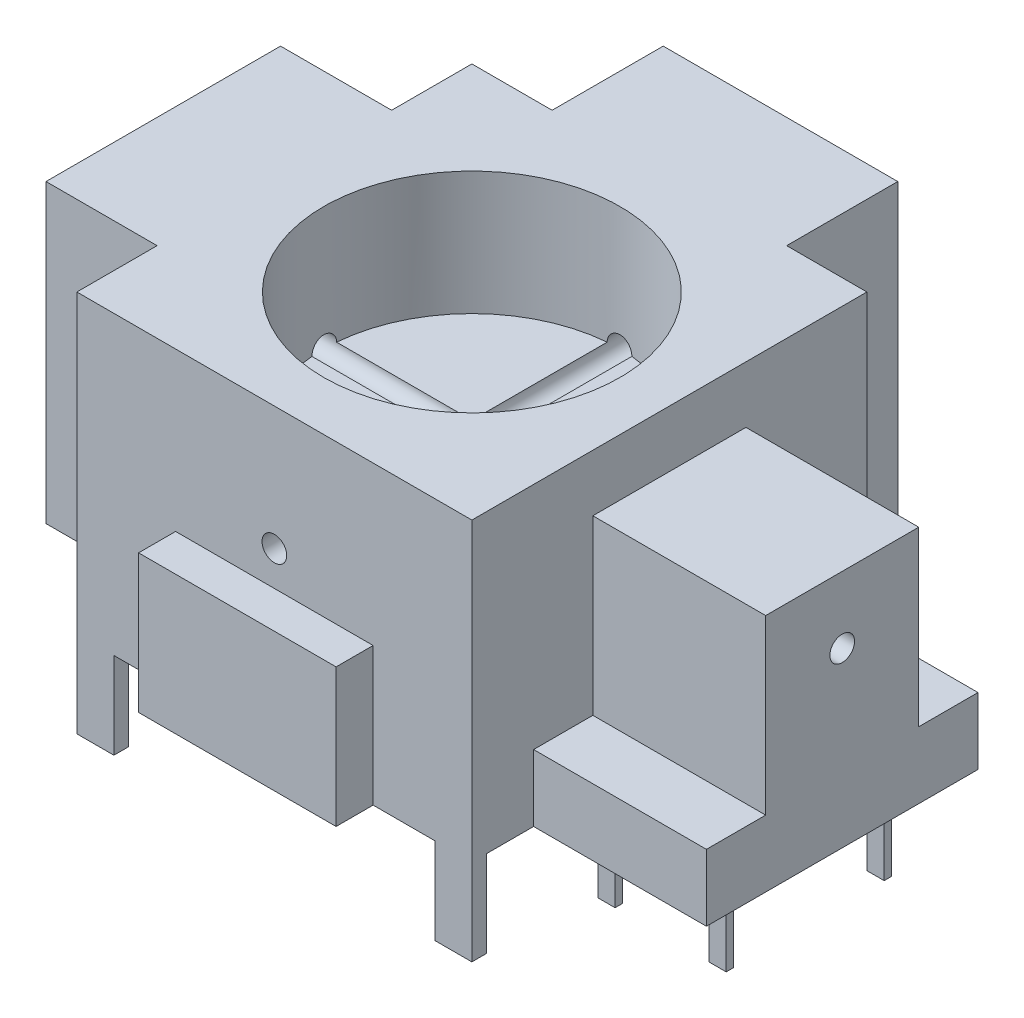
SolidWorks part; units mm, degrees
ref_plane "Front Plane" through (0, 0, 0) normal (0, 0, 1) x (1, 0, 0)
ref_plane "Top Plane" through (0, 0, 0) normal (0, 1, 0) x (1, 0, 0)
ref_plane "Right Plane" through (0, 0, 0) normal (1, 0, 0) x (0, 0, -1)
sketch "Sketch1" plane through (0, 0, 0) normal (0, 1, 0) x (1, 0, 0)
  line L1 (-8, -8) -> (8, -8)
  line L2 (-8, -8) -> (-8, 8)
  line L3 (-8, 8) -> (8, 8)
  line L4 (8, -8) -> (8, 8)
  line L5 (-8, -8) -> (8, 8) construction
  line L6 (-8, 8) -> (8, -8) construction
  point P0 (0, 0)
  dimension "D1" = 16
  dimension "D2" = 16
extrude "Boss-Extrude1" add sketch "Sketch1" along normal blind 12
sketch "Sketch2" plane through (-8, 0, 0) normal (-1, 0, 0) x (0, 0, 1)
  line L0 (-8, 0) -> (8, 0) construction
  line L1 (-4.75, 0) -> (4.75, 0)
  line L2 (-4.75, 0) -> (-4.75, 12)
  line L3 (-4.75, 12) -> (4.75, 12)
  line L4 (4.75, 0) -> (4.75, 12)
  line L5 (-8, 12) -> (8, 12) construction
  point P6 (0, 0)
  point P7 (0, 0)
  dimension "D1" = 9.5
extrude "Boss-Extrude2" add sketch "Sketch2" along normal blind 4.5
ref_axis "Axis1" through (0, 12.6, 0) along (0, -1, 0)
pattern_circular "CirPattern1" count 2 every 90 about axis through (0, 12.6, 0) along (0, -1, 0) of "Boss-Extrude2"
sketch "Sketch4" plane through (0, 0, 8) normal (0, 0, 1) x (1, 0, 0)
  line L0 (-8, 0) -> (8, 0) construction
  line L1 (-4, 0) -> (4, 0)
  line L2 (-4, 0) -> (-4, 5.6)
  line L3 (-4, 5.6) -> (4, 5.6)
  line L4 (4, 0) -> (4, 5.6)
  point P6 (0, 0)
  point P7 (0, 0)
  dimension "D1" = 5.6
  dimension "D2" = 8
extrude "Boss-Extrude3" add sketch "Sketch4" along normal blind 1.5
sketch "Sketch5" plane through (8, 0, 0) normal (1, 0, 0) x (0, 0, -1)
  line L0 (-8, 0) -> (8, 0) construction
  line L1 (-5.5, 0) -> (5.5, 0)
  line L2 (-5.5, 0) -> (-5.5, 2.7)
  line L3 (-5.5, 2.7) -> (5.5, 2.7)
  line L4 (5.5, 0) -> (5.5, 2.7)
  point P6 (0, 0)
  point P7 (0, 0)
  dimension "D1" = 11
  dimension "D2" = 2.7
extrude "Boss-Extrude4" add sketch "Sketch5" along normal blind 7
sketch "Sketch6" plane through (0, 2.7, 0) normal (0, 1, 0) x (1, 0, 0)
  line L0 (8, 5.5) -> (8, -5.5) construction
  line L1 (8, -3.1) -> (15, -3.1)
  line L2 (8, -3.1) -> (8, 3.1)
  line L3 (8, 3.1) -> (15, 3.1)
  line L4 (15, -3.1) -> (15, 3.1)
  line L5 (15, 5.5) -> (15, -5.5) construction
  point P8 (8, 0)
  point P9 (8, 0)
  dimension "D1" = 6.2
extrude "Boss-Extrude5" add sketch "Sketch6" along normal blind 7
sketch "Sketch7" plane through (0, 12, 0) normal (0, 1, 0) x (1, 0, 0)
  circle A0 centre (0, 0) radius 6
  dimension "D1" = 12
extrude "Cut-Extrude1" cut sketch "Sketch7" against normal blind 5
ref_point "Point1"
sketch "Sketch8" plane through (0, 0, 0) normal (1, 0, 0) x (0, 0, -1)
  circle A0 centre (0, 7) radius 0.5
  dimension "D1" = 1
extrude "Cut-Extrude2" cut sketch "Sketch8" against normal through all both and the other way through all
sketch "Sketch9" plane through (0, 0, 0) normal (0, 0, 1) x (1, 0, 0)
  circle A0 centre (0, 7) radius 0.5
  dimension "D1" = 1
extrude "Cut-Extrude3" cut sketch "Sketch9" against normal through all both and the other way through all
sketch "Sketch10" plane through (0, 0, 0) normal (0, -1, 0) x (1, 0, 0)
  line L0 (6.5, 8) -> (6.5, 7.4)
  line L1 (-8, 8) -> (-6.5, 8)
  line L2 (-8, 8) -> (-8, 7.4)
  line L3 (-8, 7.4) -> (-6.5, 7.4)
  line L4 (-6.5, 8) -> (-6.5, 7.4)
  line L5 (6.5, 8) -> (8, 8)
  line L6 (8, 8) -> (8, 7.4)
  line L7 (6.5, 7.4) -> (8, 7.4)
  line L8 (6.5, -7.4) -> (6.5, -8)
  line L9 (6.5, -7.4) -> (8, -7.4)
  line L10 (8, -7.4) -> (8, -8)
  line L11 (6.5, -8) -> (8, -8)
  line L12 (-8, -7.4) -> (-8, -8)
  line L13 (-8, -7.4) -> (-6.5, -7.4)
  line L14 (-6.5, -7.4) -> (-6.5, -8)
  line L15 (-8, -8) -> (-6.5, -8)
  line L16 (-11.5, -0.4) -> (-11.5, 0.4)
  line L17 (-11.5, -2.9) -> (-11.1, -2.9)
  line L18 (-11.5, -2.9) -> (-11.5, -2.1)
  line L19 (-11.5, -2.1) -> (-11.1, -2.1)
  line L20 (-11.1, -2.9) -> (-11.1, -2.1)
  line L21 (-11.5, -2.9) -> (-11.1, -2.1) construction
  line L22 (-11.5, -2.1) -> (-11.1, -2.9) construction
  line L23 (-11.5, -0.4) -> (-11.1, -0.4)
  line L24 (-11.1, -0.4) -> (-11.1, 0.4)
  line L25 (-11.5, 0.4) -> (-11.1, 0.4)
  line L26 (-11.5, 2.1) -> (-11.5, 2.9)
  line L27 (-11.5, 2.1) -> (-11.1, 2.1)
  line L28 (-11.1, 2.1) -> (-11.1, 2.9)
  line L29 (-11.5, 2.9) -> (-11.1, 2.9)
  line L30 (-12.5, -4.75) -> (-12.5, 4.75) construction
  line L31 (-2.1, -11.5) -> (-2.9, -11.5)
  line L32 (-2.9, -11.5) -> (-2.9, -11.1)
  line L33 (-2.1, -11.1) -> (-2.9, -11.1)
  line L34 (-2.1, -11.5) -> (-2.1, -11.1)
  line L35 (0.4, -11.5) -> (-0.4, -11.5)
  line L36 (-0.4, -11.5) -> (-0.4, -11.1)
  line L37 (0.4, -11.1) -> (-0.4, -11.1)
  line L38 (0.4, -11.5) -> (0.4, -11.1)
  line L39 (2.9, -11.5) -> (2.1, -11.5)
  line L40 (2.9, -11.5) -> (2.9, -11.1)
  line L41 (2.9, -11.1) -> (2.1, -11.1)
  line L42 (2.1, -11.5) -> (2.1, -11.1)
  line L43 (4.75, -12.5) -> (-4.75, -12.5) construction
  line L44 (15, -5.5) -> (8, -5.5) construction
  line L45 (12.8, -3.5) -> (13.5, -3.5)
  line L46 (12.8, -3.5) -> (12.8, -3.2)
  line L47 (12.8, -3.2) -> (13.5, -3.2)
  line L48 (13.5, -3.5) -> (13.5, -3.2)
  line L49 (12.8, -3.5) -> (13.5, -3.2) construction
  line L50 (12.8, -3.2) -> (13.5, -3.5) construction
  line L52 (8.3, -3.5) -> (8.3, -3.2)
  line L53 (8.3, -3.5) -> (9, -3.5)
  line L54 (9, -3.5) -> (9, -3.2)
  line L55 (8.3, -3.2) -> (9, -3.2)
  line L56 (8.3, 2.9) -> (8.3, 3.2)
  line L57 (8.3, 2.9) -> (9, 2.9)
  line L58 (9, 2.9) -> (9, 3.2)
  line L59 (8.3, 3.2) -> (9, 3.2)
  line L60 (12.8, 2.9) -> (12.8, 3.2)
  line L61 (12.8, 2.9) -> (13.5, 2.9)
  line L62 (13.5, 2.9) -> (13.5, 3.2)
  line L63 (12.8, 3.2) -> (13.5, 3.2)
  line L64 (15, 5.5) -> (8, 5.5) construction
  point P5 (-11.1, 0)
  point P7 (-11.3, -2.5)
  point P36 (0, -11.1)
  point P39 (13.15, -3.35)
  point P73 (9, -3.35)
  dimension "D10" = 1
  dimension "D1" = 1.5
  dimension "D2" = 0.6
  dimension "D5" = 0.4
  dimension "D6" = 0.8
  dimension "D8" = 1
  dimension "D9" = 3.3
  dimension "D12" = 0.7
  dimension "D13" = 0.3
  dimension "D14" = 2.3
  dimension "D15" = 7
  dimension "D18" = 2.3
  dimension "D19" = 2.5
  dimension "D3" = 2
  dimension "D4" = 2
  dimension "D7" = 3
  dimension "D16" = 2
  dimension "D17" = 2
  dimension "D11" = 2
extrude "Boss-Extrude6" add sketch "Sketch10" along normal blind 3.5
equation "\"D2@Sketch1\"=\"D1@Sketch1\""
